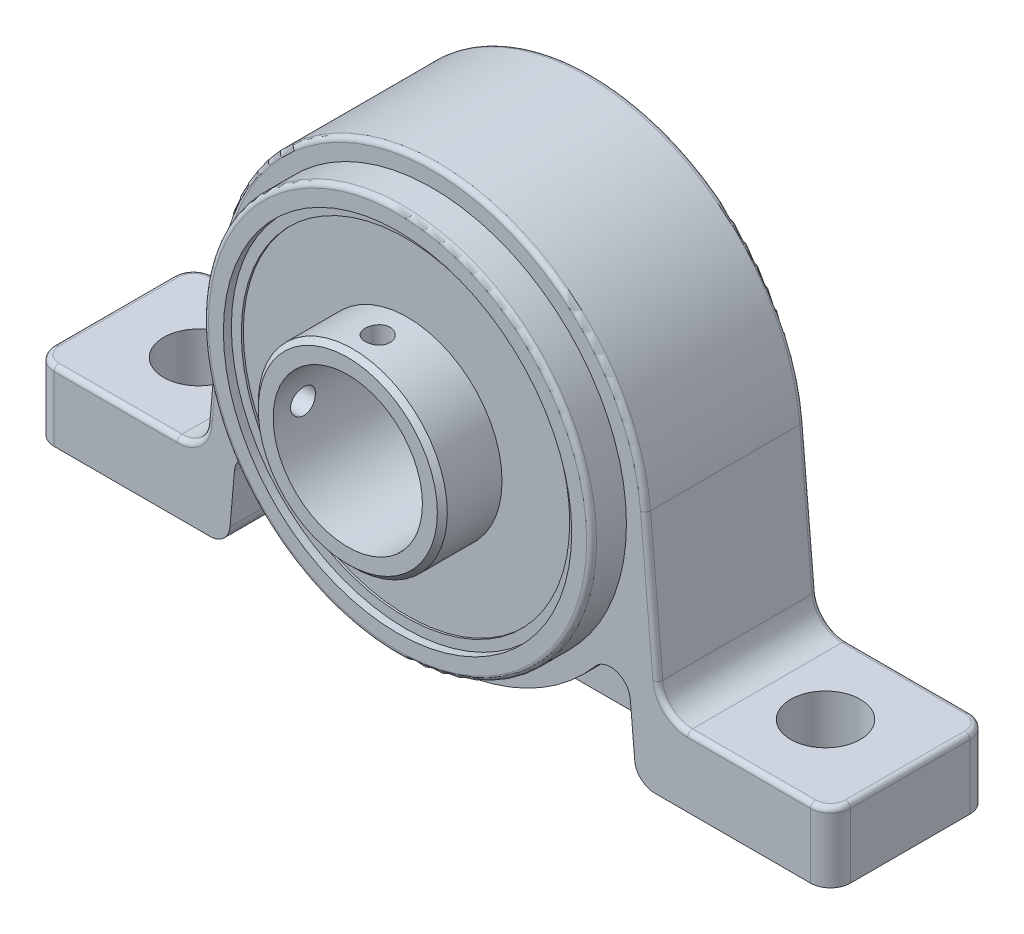
SolidWorks part; units mm, degrees
ref_plane "Front Plane" through (0, 0, 0) normal (0, 0, 1) x (1, 0, 0)
ref_plane "Top Plane" through (0, 0, 0) normal (0, 1, 0) x (1, 0, 0)
ref_plane "Right Plane" through (0, 0, 0) normal (1, 0, 0) x (0, 0, -1)
sketch "Sketch1" plane through (0, 0, 0) normal (0, 0, 1) x (1, 0, 0)
  line L0 (0, 0) -> (-11670.9506, 0) construction
  line L1 (0, 0) -> (0, 11670.9506) construction
  line L2 (-40, 0) -> (-40, 7)
  line L3 (-40, 7) -> (-25.6434, 7)
  line L4 (-40, 0) -> (-22.3281, 0)
  line L5 (-20.3357, 1.8257) -> (-19.888, 6.9429)
  line L6 (-22.6549, 9.7385) -> (-21.4182, 23.8738)
  line L7 (40, -4.905) -> (-40, -4.905) construction
  line L8 (8.5, -4.905) -> (8.5, -1.8884) construction
  line L9 (-8.5, -4.905) -> (-8.5, -1.8884) construction
  line L10 (0, 0) -> (11670.9506, 0) construction
  line L11 (22.6549, 9.7385) -> (21.4182, 23.8738)
  line L12 (20.3357, 1.8257) -> (19.888, 6.9429)
  line L13 (40, 0) -> (22.3281, 0)
  line L14 (40, 7) -> (25.6434, 7)
  line L15 (40, 0) -> (40, 7)
  circle A0 centre (0, 22) radius 7.5
  arc A1 (-16.3726, 8.0648) -> (16.3726, 8.0648) centre (0, 22) ccw
  circle A2 centre (0, 22) radius 19.5
  arc A3 (-22.6549, 9.7385) -> (-25.6434, 7) centre (-25.6434, 10) cw
  arc A4 (-20.3357, 1.8257) -> (-22.3281, 0) centre (-22.3281, 2) cw
  arc A5 (-16.3726, 8.0648) -> (-19.888, 6.9429) centre (-17.8956, 6.7685) ccw
  circle A6 centre (0, 22) radius 21.5 construction
  circle A7 centre (0, 22) radius 9.5
  circle A8 centre (0, 22) radius 17.5
  circle A9 centre (0, 22) radius 16.5
  arc A10 (16.3726, 8.0648) -> (19.888, 6.9429) centre (17.8956, 6.7685) cw
  arc A11 (20.3357, 1.8257) -> (22.3281, 0) centre (22.3281, 2) ccw
  arc A12 (22.6549, 9.7385) -> (25.6434, 7) centre (25.6434, 10) ccw
  arc A13 (21.4182, 23.8738) -> (-21.4182, 23.8738) centre (0, 22) ccw
  point P18 (0, -4.905)
  point P33 (-20.4954, 0)
  point P34 (14.3446, 20.3856)
  point P57 (20.4954, 0)
  dimension "D1" = 15
  dimension "D3" = 43
  dimension "D10" = 3
  dimension "D11" = 2
  dimension "D12" = 2
  dimension "D2" = 22
  dimension "D4" = 80
  dimension "D6" = 7
  dimension "D7" = 3
  dimension "D9" = 85
  dimension "D8" = 2
  dimension "D13" = 2
  dimension "D14" = 2
  dimension "D15" = 1
extrude "B" add sketch "Sketch1" along normal blind 16 contours L11 A13 L6 A3 L3 L2 L4 A4 L5 A5 A1 A10 L12 A11 L13 L15 L14 A12 A2 region at (-39.0894, 3.5, 0)
extrude "B1S" add sketch "Sketch1<3>" along normal blind 16.5 from offset 3 contours A2 A8 region at (-18.9485, 22, 0)
sketch "Sketch1<3>" plane through (0, 0, 0) normal (0, 0, 1) x (1, 0, 0) same geometry as "Sketch1"
extrude "Boss-Extrude3" add sketch "Sketch1<4>" along normal blind 15.5 from offset 3.2 contours A8 A9 region at (-17.005, 22, 0)
sketch "Sketch1<4>" plane through (0, 0, 0) normal (0, 0, 1) x (1, 0, 0) same geometry as "Sketch1"
extrude "Boss-Extrude4" add sketch "Sketch1<6>" along normal blind 15 from offset 3.5 contours A9 A7 region at (-16.0333, 22, 0)
sketch "Sketch1<6>" plane through (0, 0, 0) normal (0, 0, 1) x (1, 0, 0) same geometry as "Sketch1"
extrude "A" add sketch "Sketch1<7>" along normal blind 21.5 from offset 3 contours A7 A0 region at (-9.2313, 22, 0)
sketch "Sketch1<7>" plane through (0, 0, 0) normal (0, 0, 1) x (1, 0, 0) same geometry as "Sketch1"
ref_plane "Plane1" through (0, 0, 8) normal (0, 0, 1) x (1, 0, 0)
sketch "Sketch2" plane through (0, 0, 8) normal (0, 0, 1) x (1, 0, 0)
  line L0 (22.3281, 0) -> (-22.3281, 0)
  line L1 (-22.3281, 0) -> (-22.3281, 5.5)
  line L2 (-22.3281, 5.5) -> (22.3281, 5.5)
  line L3 (22.3281, 5.5) -> (22.3281, 0)
  dimension "D1" = 44.6562
  dimension "D2" = 5.5
extrude "Boss-Extrude6" add sketch "Sketch2" along normal mid plane 4
sketch "Sketch3" plane through (0, 0, 0) normal (1, 0, 0) x (0, 0, -1)
  line L0 (-18, 22) -> (49982, 22) construction
  line L1 (-24.5, 31.5) -> (-24.5, 12.5) construction
  line L2 (-21.5, 22) -> (-21.5, -49978) construction
  line L3 (-18.5, 31.5) -> (-24.5, 31.5) construction
  circle A0 centre (-21.5, 22) radius 1.25
  point P4 (-24.5, 22)
  point P9 (-21.5, 31.5)
  dimension "D1" = 2.5
extrude "Cut-Extrude1" cut sketch "Sketch3" against normal up to next
pattern_circular "CirPattern1" count 2 over 90 about axis through (0, 22, 24.5) along (0, 0, -1) of "Cut-Extrude1"
fillet "Fillet1" radius 2 4 edges at (-40, 3.5, 0) (-40, 3.5, 16) (40, 3.5, 0) (40, 3.5, 16)
fillet "Fillet2" radius 0.5 21 edges at (22.0365, 16.8062, 16) (23.6167, 7.7882, 16) (31.8217, 7, 16) (39.4142, 7, 15.4142) (40, 7, 8) (39.4142, 7, 0.5858) (31.8217, 7, 0) (23.6167, 7.7882, 0) (22.0365, 16.8062, 0) (0, 43.5, 0) (-22.0365, 16.8062, 0) (-23.6167, 7.7882, 0) (-31.8217, 7, 0) (-39.4142, 7, 0.5858) (-40, 7, 8) (-39.4142, 7, 15.4142) (-31.8217, 7, 16) (-23.6167, 7.7882, 16) (-22.0365, 16.8062, 16) (0, 43.5, 16) (19.5, 22, 19.5)
fillet "Fillet3" radius 1 1 edges at (19.5, 22, 0)
chamfer "Chamfer1" distance 0.5 angle 45 1 edges at (9.5, 22, 24.5)
sketch "Sketch4" plane through (0, 7, 0) normal (0, 1, 0) x (1, 0, 0)
  line L0 (40, -8) -> (-40, -8) construction
  line L1 (40, -2) -> (40, -14) construction
  line L2 (-40, -14) -> (-40, -2) construction
  line L3 (-40, -8) -> (0, 0) construction
  line L4 (0, 0) -> (0, -24) construction
  line L5 (9.5, -24) -> (-9.5, -24) construction
  circle A0 centre (31.5, -8) radius 3.5
  circle A1 centre (-31.5, -8) radius 3.5
  dimension "D1" = 7
  dimension "D2" = 63
extrude "J" cut sketch "Sketch4" against normal through all
equation "\"D1@Boss-Extrude3\"= \"D1@B1S\" - 1"
equation "\"D1@Boss-Extrude4\"= \"D1@Boss-Extrude3\" - 0.5"
equation "\"D1@A\"=\"D1@B1S\" + 5"
equation "\"B\"= \"D1@B\""
equation "\"A\"= \"D1@B1S\""
equation "\"Bore side\"= \"D1@Sketch1\""
equation "\"H2\"= \"D3@Sketch1\""
equation "\"H\"= \"D2@Sketch1\""
equation "\"L\"= \"D4@Sketch1\""
equation "\"T\"= \"D6@Sketch1\""
equation "\"Hold\"= \"D1@Sketch4\""
